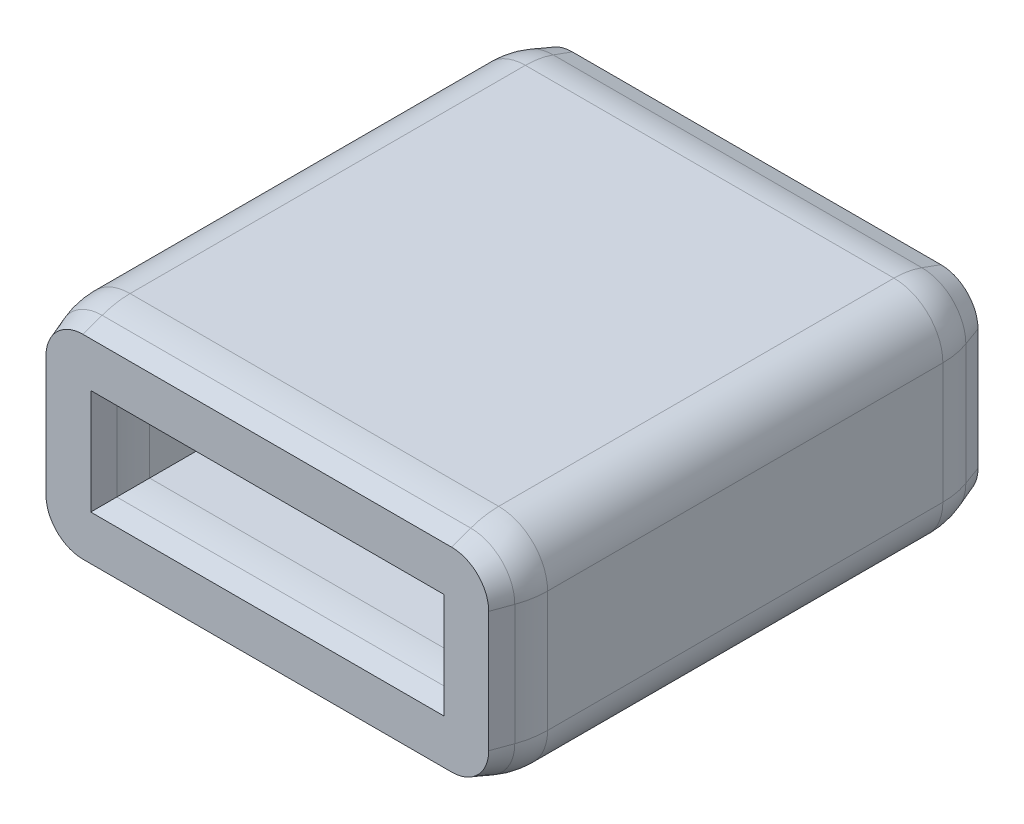
SolidWorks part; units mm, degrees
ref_plane "Front Plane" through (0, 0, 0) normal (0, 0, 1) x (1, 0, 0)
ref_plane "Top Plane" through (0, 0, 0) normal (0, 1, 0) x (1, 0, 0)
ref_plane "Right Plane" through (0, 0, 0) normal (1, 0, 0) x (0, 0, -1)
sketch "Profile Sketch" plane through (0, 0, 0) normal (0, 0, 1) x (1, 0, 0)
  line L0 (0, 1.25) -> (0, 3.35) construction
  line L1 (-5.05, -1.25) -> (5.05, -1.25)
  line L2 (-5.05, -1.25) -> (-5.05, 1.25)
  line L3 (-5.05, 1.25) -> (5.05, 1.25)
  line L4 (5.05, -1.25) -> (5.05, 1.25)
  line L5 (-5.05, -1.25) -> (5.05, 1.25) construction
  line L6 (-5.05, 1.25) -> (5.05, -1.25) construction
  line L7 (-7.15, -3.35) -> (7.15, -3.35)
  line L8 (-7.15, -3.35) -> (-7.15, 3.35)
  line L9 (-7.15, 3.35) -> (7.15, 3.35)
  line L10 (7.15, -3.35) -> (7.15, 3.35)
  line L11 (-7.15, -3.35) -> (7.15, 3.35) construction
  line L12 (-7.15, 3.35) -> (7.15, -3.35) construction
  line L13 (-5.05, 0) -> (-7.15, 0) construction
  point P0 (0, 0)
  point P6 (0, 0)
  dimension "D1" = 10.1
  dimension "D2" = 2.1
  dimension "D3" = 2.5
extrude "Profile Extrude" add sketch "Profile Sketch" along normal blind 15
fillet "Outside Corner Fillets" radius 1.5 4 edges at (7.15, 3.35, 7.5) (7.15, -3.35, 7.5) (-7.15, 3.35, 7.5) (-7.15, -3.35, 7.5)
fillet "Corner Fillets" [suppressed] radius 1
fillet "Inlet Fillets" [suppressed] radius 1
chamfer "End 1 Chamfer" distance 1 angle 20 12 edges at (6.7107, 2.9107, 0) (7.15, 0, 0) (6.7107, -2.9107, 0) (0, -3.35, 0) (-6.7107, -2.9107, 0) (-7.15, 0, 0) (-6.7107, 2.9107, 0) (0, 3.35, 0) (5.05, 0, 15) (0, 1.25, 15) (-5.05, 0, 15) (0, -1.25, 15) first distance on face at (6.5553, 2.7553, 7.5) first distance on face at (7.15, 0, 7.5) first distance on face at (6.5553, -2.7553, 7.5) first distance on face at (0, -3.35, 7.5) first distance on face at (-6.5553, -2.7553, 7.5) first distance on face at (-7.15, 0, 7.5) first distance on face at (-6.5553, 2.7553, 7.5) first distance on face at (0, 3.35, 7.5) first distance on face at (5.05, 0, 7.5) first distance on face at (0, 1.25, 7.5) first distance on face at (-5.05, 0, 7.5) first distance on face at (0, -1.25, 7.5)
chamfer "End 2 Chamfer" distance 1 angle 20 12 edges at (0, -3.35, 15) (6.7107, -2.9107, 15) (-6.7107, -2.9107, 15) (7.15, 0, 15) (-7.15, 0, 15) (6.7107, 2.9107, 15) (-6.7107, 2.9107, 15) (0, 3.35, 15) (5.05, 0, 0) (0, 1.25, 0) (-5.05, 0, 0) (0, -1.25, 0) first distance on face at (0, -3.35, 8) first distance on face at (6.5553, -2.7553, 8) first distance on face at (-6.5553, -2.7553, 8) first distance on face at (7.15, 0, 8) first distance on face at (-7.15, 0, 8) first distance on face at (6.5553, 2.7553, 8) first distance on face at (-6.5553, 2.7553, 8) first distance on face at (0, 3.35, 8) first distance on face at (5.05, 0, 7) first distance on face at (0, 1.25, 7) first distance on face at (-5.05, 0, 7) first distance on face at (0, -1.25, 7)
fillet "Transition Fillets" radius 2.5 24 edges at (6.7107, 2.9107, 1) (7.15, 0, 1) (6.7107, -2.9107, 1) (0, -3.35, 1) (-6.7107, -2.9107, 1) (-7.15, 0, 1) (-6.7107, 2.9107, 1) (0, 3.35, 1) (-6.7107, 2.9107, 14) (-7.15, 0, 14) (-6.7107, -2.9107, 14) (0, -3.35, 14) (6.7107, -2.9107, 14) (7.15, 0, 14) (6.7107, 2.9107, 14) (0, 3.35, 14) (0, 1.25, 1) (0, 1.25, 14) (5.05, 0, 14) (-5.05, 0, 14) (0, -1.25, 14) (-5.05, 0, 1) (0, -1.25, 1) (5.05, 0, 1)
